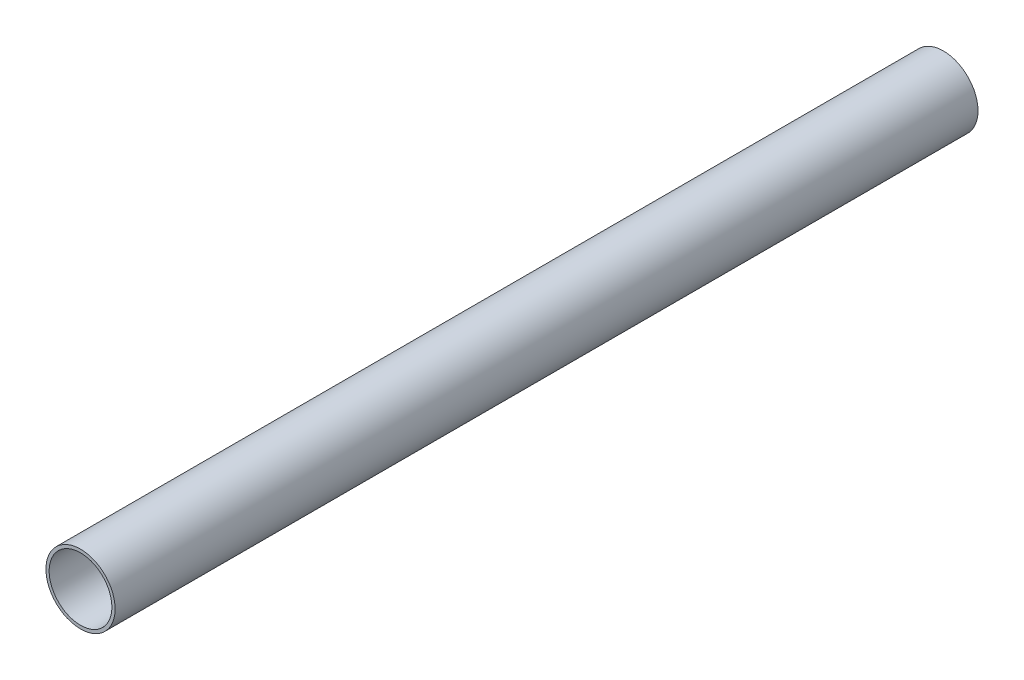
SolidWorks part; units mm, degrees
ref_plane "Front Plane" through (0, 0, 0) normal (0, 0, 1) x (1, 0, 0)
ref_plane "Top Plane" through (0, 0, 0) normal (0, 1, 0) x (1, 0, 0)
ref_plane "Right Plane" through (0, 0, 0) normal (1, 0, 0) x (0, 0, -1)
sketch "Sketch2" plane through (0, 0, 0) normal (0, 0, 1) x (1, 0, 0)
  circle A0 centre (0, 0) radius 10
sketch "Sketch3" plane through (0, 0, 0) normal (0, 0, 1) x (1, 0, 0)
  circle A0 centre (0, 0) radius 11.0227
extrude "Boss-Extrude1" add sketch "Sketch3" along normal blind 275
extrude "Cut-Extrude1" cut sketch "Sketch2" against normal blind 275 and the other way blind 275 contours A0
